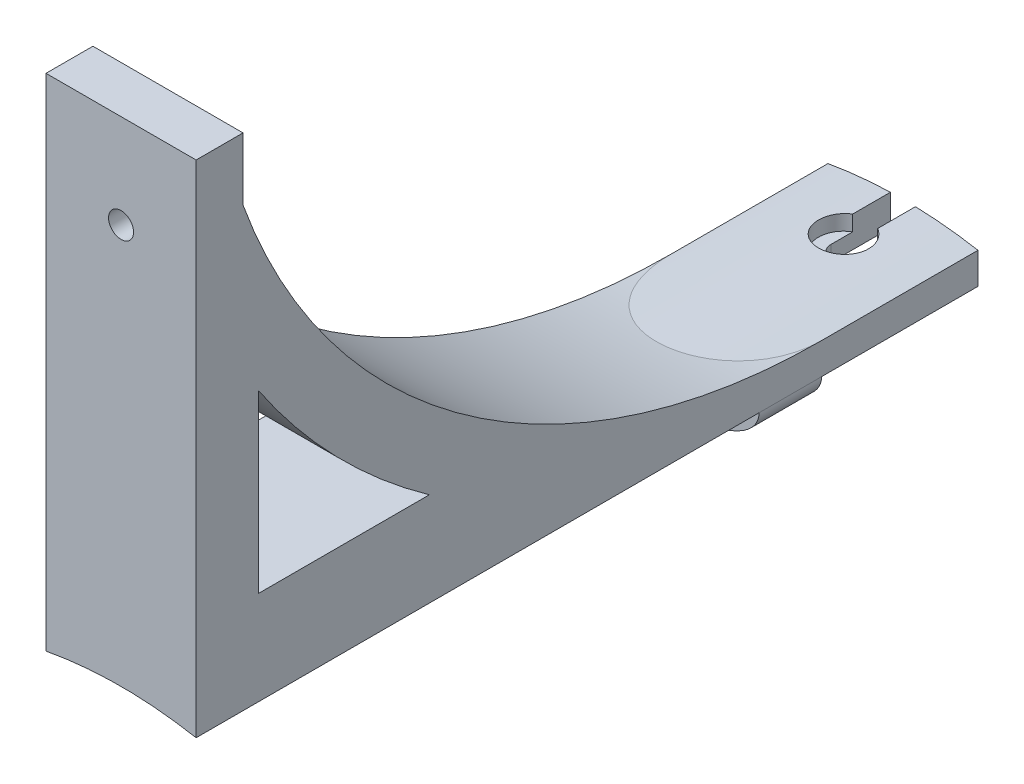
SolidWorks part; units mm, degrees
ref_plane "Front Plane" through (0, 0, 0) normal (0, 0, 1) x (1, 0, 0)
ref_plane "Top Plane" through (0, 0, 0) normal (0, 1, 0) x (1, 0, 0)
ref_plane "Right Plane" through (0, 0, 0) normal (1, 0, 0) x (0, 0, -1)
sketch "Sketch1" plane through (0, 0, 0) normal (0, 0, 1) x (1, 0, 0)
  line L0 (-12, 69.1371) -> (-12, 64.1371)
  line L1 (12, 69.1371) -> (12, 64.1371)
  line L2 (-2, 68.2207) -> (-2, 65.2193) construction
  line L3 (2, 65.2193) -> (2, 68.2207) construction
  line L4 (-2, 68.2207) -> (-2, 65.2193) construction
  line L5 (2, 65.2193) -> (2, 68.2207) construction
  line L6 (-2, 66.72) -> (2, 66.72) construction
  circle A0 centre (0, 0) radius 65.25 construction
  arc A2 (12, 64.1371) -> (-12, 64.1371) centre (0, 0) ccw
  arc A3 (12, 69.1371) -> (-12, 69.1371) centre (0, 1.9503) ccw
  point P3 (-12, 70.915)
  point P4 (0, 0)
  dimension "D3" = 5
  dimension "D1" = 10
  dimension "D2" = 10
extrude "Boss-Extrude1" add sketch "Sketch1" along normal blind 100 and the other way blind 25
sketch "Sketch2" plane through (0, 0, 0) normal (0, 0, 1) x (1, 0, 0)
  line L0 (12, 64.1371) -> (-12, 64.1371) construction
  arc A0 (12, 64.1371) -> (-12, 64.1371) centre (0, 0) ccw construction
  arc A1 (12, 64.1371) -> (-12, 64.1371) centre (0, 0) ccw
  arc A2 (12, 69.1371) -> (-12, 69.1371) centre (0, 1.9503) ccw construction
  ellipse E0 centre (0, 64.1371) end of major axis (12, 64.1371) minor radius 6.0632 (-12, 64.1371) -> (12, 64.1371) ccw
  point P13 (0, 67.2088)
  point P14 (0, 0)
  point P18 (0, 70.2003)
extrude "Boss-Extrude2" add sketch "Sketch2" along normal blind 10
sketch "Sketch3" plane through (-12, 0, 0) normal (-1, 0, 0) x (0, 0, 1)
  line L0 (-25, 69.1371) -> (0, 69.1371) construction
  line L1 (-25, 69.1371) -> (100, 69.1371) construction
  line L2 (92.5, 134.1371) -> (92.5, 144.1371)
  line L3 (100, 69.1371) -> (100, 144.1371)
  line L4 (92.5, 144.1371) -> (100, 144.1371)
  line L5 (100, 69.1371) -> (0, 69.1371)
  line L6 (90, 79.1371) -> (90, 107.183)
  line L7 (90, 107.183) -> (90, 107.183)
  line L8 (90, 107.183) -> (90, 107.183)
  line L9 (90, 79.1371) -> (62.7112, 79.1371)
  arc A0 (0, 69.1371) -> (92.5, 134.1371) centre (0, 167.4544) ccw
  arc A1 (62.7112, 79.1371) -> (90, 107.183) centre (0, 167.4544) ccw
  point P16 (0, 0)
  point P17 (0, 0)
  point P18 (90, 97.33)
  point P19 (0, 0)
  point P21 (0, 0)
  point P22 (0, 67.1868)
  dimension "D1" = 7.5
  dimension "D2" = 10
  dimension "D3" = 75
  dimension "D4" = 10
extrude "Boss-Extrude4" add sketch "Sketch3" against normal up to surface (24 mm away) up to face at (12, 65.8037, 26.6667)
sketch "Sketch5" plane through (0, 0, -25) normal (0, 0, -1) x (-1, 0, 0)
  line L0 (0, 65.25) -> (0, 70.2003) construction
  arc A0 (12, 64.1371) -> (-12, 64.1371) centre (0, 0) ccw construction
  arc A1 (12, 69.1371) -> (-12, 69.1371) centre (0, 1.9503) ccw construction
ref_plane "Plane1" through (0, 70.2003, -25) normal (0, 1, 0) x (1, 0, 0)
sketch "Sketch8" plane through (0, 70.2003, -25) normal (0, 1, 0) x (1, 0, 0)
  line L0 (2, -9.5) -> (2, 0)
  line L1 (12, 0) -> (-12, 0) construction
  line L2 (2, 0) -> (-2, 0)
  line L3 (-2, 0) -> (-2, -9.5)
  circle A0 centre (0, -9.5) radius 2 construction
  arc A1 (-2, -9.5) -> (2, -9.5) centre (0, -9.5) ccw
extrude "Cut-Extrude3" cut sketch "Sketch8" against normal through all both and the other way through all
sketch "Sketch9" plane through (0, 70.2003, -25) normal (0, 1, 0) x (1, 0, 0)
  circle A0 centre (0, -9.5) radius 4
  dimension "D1" = 8
extrude "Cut-Extrude4" cut sketch "Sketch9" against normal blind 2.5
sketch "Sketch10" plane through (0, 0, 92.5) normal (0, 0, -1) x (-1, 0, 0)
  line L0 (0, 144.1371) -> (0, 129.1371) construction
  line L1 (-12, 144.1371) -> (12, 144.1371) construction
  circle A0 centre (0, 129.1371) radius 2
  dimension "D2" = 4
  dimension "D1" = 15
extrude "Cut-Extrude5" cut sketch "Sketch10" against normal through all both and the other way through all
sketch "Sketch11" plane through (0, 0, 92.5) normal (0, 0, -1) x (-1, 0, 0)
  circle A2 centre (0, 129.1371) radius 4
  circle A3 centre (0, 129.1371) radius 4
  dimension "D1" = 2
extrude "Cut-Extrude6" cut sketch "Sketch11" along normal through all
